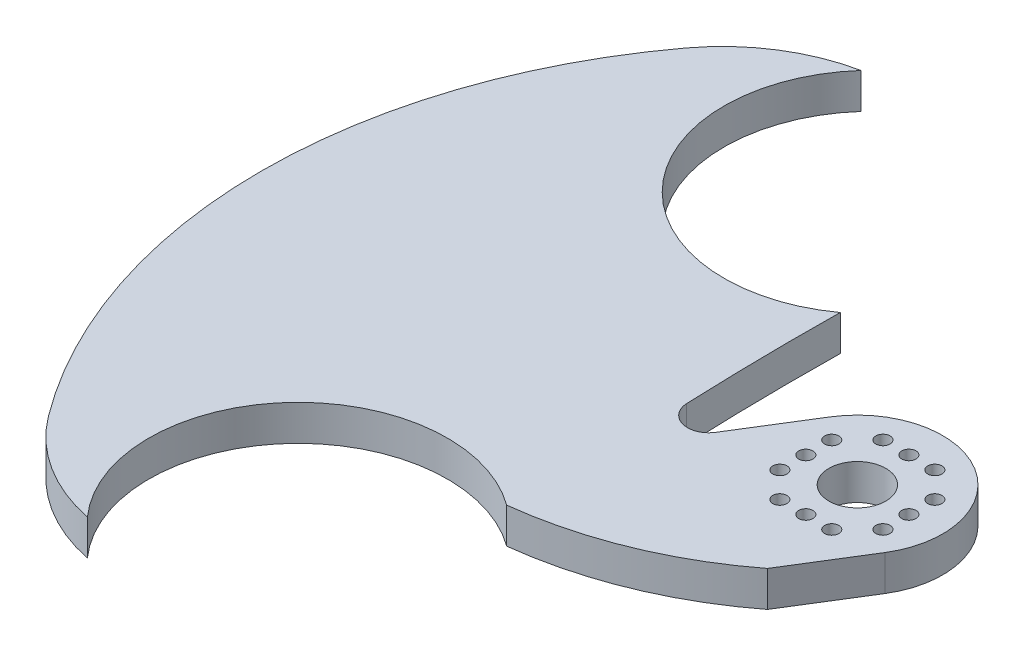
SolidWorks part; units mm, degrees
ref_plane "Plan de face" through (0, 0, 0) normal (0, 0, 1) x (1, 0, 0)
ref_plane "Plan de dessus" through (0, 0, 0) normal (0, 1, 0) x (1, 0, 0)
ref_plane "Plan de droite" through (0, 0, 0) normal (1, 0, 0) x (0, 0, -1)
sketch "Esquisse1" plane through (0, 0, 0) normal (0, 1, 0) x (1, 0, 0)
  line L0 (7.25, 3.65) -> (7.25, -3.65) construction
  line L1 (0, 0) -> (7.25, 0) construction
  line L3 (-10.1964, 6.3273) -> (-16.3454, -3.5818)
  line L5 (3.8691, -16.5236) -> (10.1964, -6.3273)
  line L12 (0, 0) -> (-80, 0) construction
  line L13 (-45.2, -33.6) -> (-45.2, 26.229) construction
  line L14 (-55, 0) -> (-45.2, -33.6) construction
  arc A0 (-22.1812, -27.1474) -> (3.8691, -16.5236) centre (-28.2564, 25) ccw
  arc A1 (-21.8919, -2.1226) -> (-16.3454, -3.5818) centre (-18.8944, -2) ccw
  arc A2 (-21.8919, -2.1226) -> (-22.1812, 19.7764) centre (373.6519, 14.054) cw
  arc A3 (-6.1357, 25.2973) -> (-8.9173, -32.4379) centre (-5.136, -3.6855) ccw construction
  circle A4 centre (0, 0) radius 4
  circle A5 centre (7.25, -3.65) radius 1
  circle A6 centre (7.25, 0) radius 1
  circle A7 centre (7.25, 3.65) radius 1
  circle A8 centre (3.65, -7.25) radius 1
  circle A9 centre (0, -7.25) radius 1
  circle A10 centre (-3.65, -7.25) radius 1
  circle A11 centre (-7.25, -3.65) radius 1
  circle A12 centre (-7.25, 0) radius 1
  circle A13 centre (-7.25, 3.65) radius 1
  circle A14 centre (-3.65, 7.25) radius 1
  circle A15 centre (0, 7.25) radius 1
  circle A16 centre (3.65, 7.25) radius 1
  arc A36 (-45.2, 26.229) -> (-45.2, -33.6) centre (-5.136, -3.6855) ccw construction
  arc A37 (-65.232, 41.1862) -> (-65.232, -48.5572) centre (-5.136, -3.6855) ccw
  arc A40 (-65.232, -48.5572) -> (-50.2176, -58.0913) centre (-45.2, -33.6) ccw
  arc A41 (10.1964, -6.3273) -> (-10.1964, 6.3273) centre (0, 0) ccw
  arc A42 (-5.2135, 46.3144) -> (-36.2654, -42.813) centre (-5.136, -3.6855) ccw construction
  arc A43 (-50.2176, 50.7203) -> (-22.1812, 19.7764) centre (-34.5243, 36.766) ccw
  arc A44 (-50.2176, 50.7203) -> (-65.232, 41.1862) centre (-45.2, 26.229) ccw
  arc A45 (-22.1812, -27.1474) -> (-50.2176, -58.0913) centre (-34.5243, -44.1371) ccw
  point P39 (0, 0)
  point P78 (-56.6847, 2.6915)
  point P85 (-55, 0)
  dimension "D4" = 25
  dimension "D5" = 12
  dimension "D6" = 21
  dimension "D7" = 25
  dimension "D8" = 25
  dimension "D9" = 7.25
  dimension "D10" = 3
  dimension "D11" = 19
  dimension "D18" = 80
  dimension "D20" = 75
  dimension "D26" = 12
  dimension "D13" = 50
  dimension "D14" = 21
  dimension "D12" = 2
  dimension "D15" = 7.3
  dimension "D22" = 35
  dimension "D23" = 90
  dimension "D24" = 28
  dimension "D25" = 25
  dimension "D30" = 15
  dimension "D32" = 15
extrude "Boss.-Extru.1" add sketch "Esquisse1" along normal blind 5
